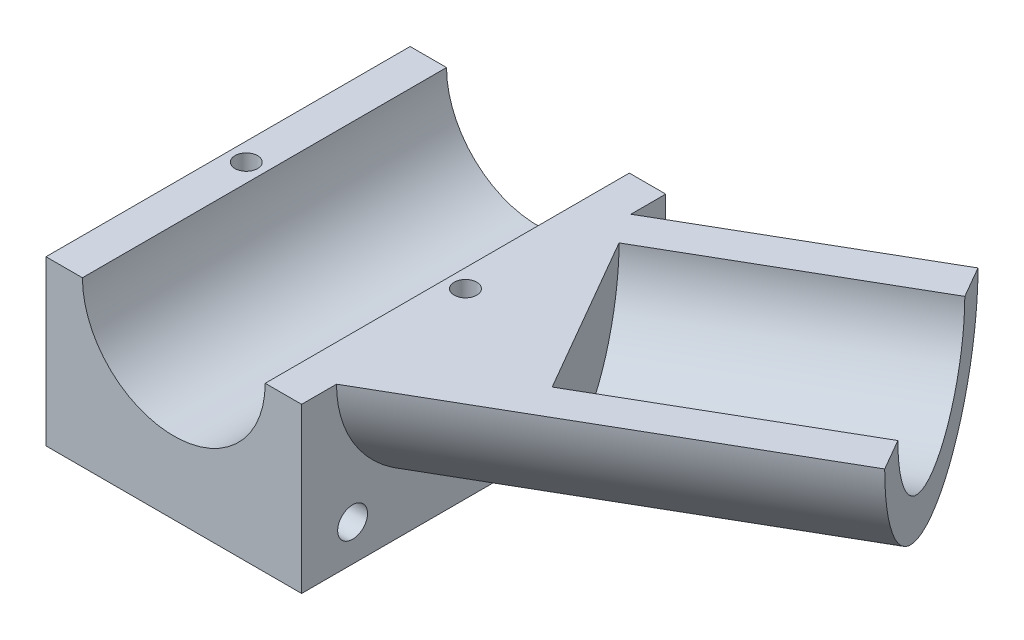
SolidWorks part; units mm, degrees
material "PLA"
ref_plane "Front Plane" through (0, 0, 0) normal (0, 0, 1) x (1, 0, 0)
ref_plane "Top Plane" through (0, 0, 0) normal (0, 1, 0) x (1, 0, 0)
ref_plane "Right Plane" through (0, 0, 0) normal (1, 0, 0) x (0, 0, -1)
sketch "Sketch1" plane through (0, 0, 0) normal (0, 0, 1) x (1, 0, 0)
  line L0 (-17.55, 22.5) -> (-17.55, 0)
  line L1 (55, 0) -> (-55, 0) construction
  line L2 (-17.55, 0) -> (17.55, 0)
  line L3 (17.55, 0) -> (17.55, 22.5)
  line L4 (-17.55, 22.5) -> (-12.55, 22.5)
  line L5 (17.55, 22.5) -> (12.55, 22.5)
  line L6 (0, -44.7868) -> (0, 44.7868) construction
  arc A0 (-12.55, 22.5) -> (12.55, 22.5) centre (0, 22.5) ccw
  dimension "D1" = 12.55
  dimension "D2" = 22.5
  dimension "D3" = 5
extrude "Boss-Extrude1" add sketch "Sketch1" along normal mid plane 50
sketch "Sketch2" plane through (0, 22.5, 0) normal (0, 1, 0) x (1, 0, 0)
  line L1 (-17.55, -25) -> (-17.55, 25) construction
  line L2 (12.55, -25) -> (12.55, 25) construction
  line L3 (-44.2539, 0) -> (44.2539, 0) construction
  circle A0 centre (-15.05, 0) radius 1.55
  circle A1 centre (15.05, 0) radius 1.55
  point P4 (0, 0)
  dimension "D1" = 3.1
  dimension "D4" = 2.5
  dimension "D5" = 2.5
extrude "Cut-Extrude1" cut sketch "Sketch2" against normal up to surface (22.5 mm away) up to face at (0, 0, 0)
sketch "Construct1" plane through (0, 0, 0) normal (0, 1, 0) x (1, 0, 0)
  line L0 (17.55, 0) -> (43.5308, 15) construction
  line L1 (-44.2539, 0) -> (44.2539, 0) construction
  line L2 (26.3131, 14.8218) -> (34.7676, 0.1782) construction
  line L3 (17.55, -25) -> (17.55, 25) construction
  point P6 (30.5404, 7.5)
  point P7 (30.5404, 7.5)
  point P8 (0, 0)
  point P9 (0, 0)
  point P10 (0, 0)
  point P11 (20.5502, 0)
  point P12 (0, 0)
  dimension "D1" = 30
  dimension "D2" = 15
ref_plane "LegBuildPlane" through (26.1529, 0, -15.0994) normal (0.866, 0, -0.5) x (-0.5, 0, -0.866)
sketch "Sketch5" plane through (26.1529, 0, -15.0994) normal (0.866, 0, -0.5) x (-0.5, 0, -0.866)
  line L0 (-26.275, 22.5) -> (-21.325, 22.5)
  line L1 (3.775, 22.5) -> (8.725, 22.5)
  line L2 (-0.3205, 0) -> (-17.2295, 0) construction
  arc A0 (-21.325, 22.5) -> (3.775, 22.5) centre (-8.775, 22.5) ccw
  arc A1 (-26.275, 22.5) -> (8.725, 22.5) centre (-8.775, 22.5) ccw
  point P9 (-8.775, 0)
  dimension "D1" = 17.5
  dimension "D2" = 12.55
  dimension "D3" = 22.5
  dimension "D4" = 0
extrude "Boss-Extrude2" add sketch "Sketch5" against normal up to surface and the other way blind 30 up to face at (17.55, 11.25, 0)
sketch "Sketch7" plane through (0, 22.5, 0) normal (0, 1, 0) x (1, 0, 0)
  line L0 (17.55, 0) -> (43.5308, 15) construction
  line L1 (62.7961, 11.6314) -> (50.2461, 33.3686) construction
  circle A0 centre (43.5308, 15) radius 1.55
  dimension "D1" = 3.1
  dimension "D2" = 15
extrude "Cut-Extrude2" cut sketch "Sketch7" against normal up to surface (17.4828 mm away) up to face at (37.0356, 13.75, -11.25)
sketch "Sketch9" plane through (-17.55, 0, 0) normal (-1, 0, 0) x (0, 0, 1)
  line L0 (25, 22.5) -> (25, 0) construction
  line L1 (-14.8218, 0) -> (-0.1782, 0) construction
  circle A0 centre (-18, 5) radius 2.05
  circle A1 centre (18, 5) radius 2.05
  point P8 (0, 0)
  dimension "D3" = 4.1
  dimension "D1" = 7
  dimension "D2" = 36
  dimension "D4" = 5
extrude "Cut-Extrude3" cut sketch "Sketch9" against normal up to surface (35.1 mm away) up to face at (17.55, 12.0833, 0)
sketch "Construct2" plane through (0, 22.5, 0) normal (0, 1, 0) x (1, 0, 0)
  line L0 (32.6981, -5.7457) -> (20.1481, 15.9915) construction
  line L2 (62.7961, 11.6314) -> (17.55, -14.4915) construction
  line L3 (50.2461, 33.3686) -> (17.55, 14.4915) construction
  line L4 (17.55, 0) -> (26.4231, 5.1229) construction
  line L11 (-44.2539, 0) -> (44.2539, 0) construction
  point P2 (29.3979, -5.1083)
  point P4 (0, 0)
  point P6 (0, 0)
  point P7 (0, 0)
  point P11 (0, 0)
  point P19 (0, 0)
  dimension "D1" = 3
  dimension "D2" = 90
ref_plane "LegBuildPlane2" through (22.0356, 0, -12.7222) normal (0.866, 0, -0.5) x (-0.5, 0, -0.866)
sketch "Sketch12" plane through (22.0356, 0, -12.7222) normal (0.866, 0, -0.5) x (-0.5, 0, -0.866)
  line L0 (-21.325, 22.5) -> (3.775, 22.5)
  arc A0 (-21.325, 22.5) -> (3.775, 22.5) centre (-8.775, 22.5) ccw
extrude "Boss-Extrude5" add sketch "Sketch12" against normal up to surface (3 mm away) up to face at (17.55, 16.225, 0)
equation "\"TubeDiam\"=12.55"
equation "\"D1@Sketch1\"=\"TubeDiam\""
equation "\"D2@Sketch1\"=\"ClampHeight\""
equation "\"MountLength\"=50"
equation "\"D1@Boss-Extrude1\"=\"MountLength\""
equation "\"MountHoleSize\"=3.1"
equation "\"D1@Sketch2\"=\"MountHoleSize\""
equation "\"LipWidth\"= 5"
equation "\"D3@Sketch1\"=\"LipWidth\""
equation "\"D4@Sketch2\"=\"LipWidth\"/2"
equation "\"D5@Sketch2\"=\"LipWidth\"/2"
equation "\"LegDiam\"=12.55"
equation "\"LegThickness\" = \"TubeDiam\" + 4.95"
equation "\"D1@Sketch5\"=\"LegThickness\""
equation "\"D2@Sketch5\"=\"TubeDiam\""
equation "\"ClampHeight\"= \"TubeDiam\" + 9.95"
equation "\"D3@Sketch5\"=\"ClampHeight\""
equation "\"D1@Sketch7\"=\"MountHoleSize\""
equation "\"HubHoleDist\"=7"
equation "\"D1@Sketch9\"=\"HubHoleDist\""
equation "\"D2@Sketch9\"=\"MountLength\" - 2 *\"HubHoleDist\""
equation "\"HubHoleSize\"=4.1"
equation "\"D3@Sketch9\"=\"HubHoleSize\""
